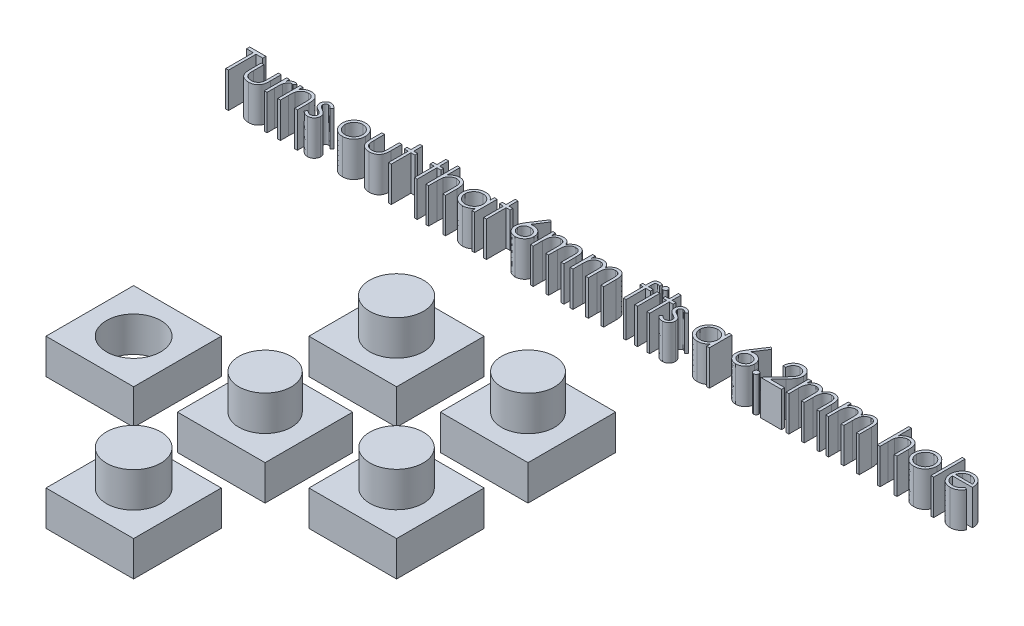
SolidWorks part; units mm, degrees
ref_plane "Front Plane" through (0, 0, 0) normal (0, 0, 1) x (1, 0, 0)
ref_plane "Top Plane" through (0, 0, 0) normal (0, 1, 0) x (1, 0, 0)
ref_plane "Right Plane" through (0, 0, 0) normal (1, 0, 0) x (0, 0, -1)
sketch "Sketch1" plane through (0, 0, 0) normal (0, 1, 0) x (1, 0, 0)
  line L0 (-52.5791, 0) -> (55.194, 0) construction
  line L1 (0, 46.4218) -> (0, -38.957) construction
  line L3 (-5, -5) -> (5, -5)
  line L4 (-5, -5) -> (-5, 5)
  line L5 (-5, 5) -> (5, 5)
  line L6 (5, -5) -> (5, 5)
  line L7 (-5, -5) -> (5, 5) construction
  line L8 (-5, 5) -> (5, -5) construction
  line L9 (-20, -5) -> (-10, -5)
  line L10 (-20, -5) -> (-20, 5)
  line L11 (-20, 5) -> (-10, 5)
  line L12 (-10, -5) -> (-10, 5)
  line L13 (-20, -5) -> (-10, 5) construction
  line L14 (-20, 5) -> (-10, -5) construction
  line L16 (10, -5) -> (20, -5)
  line L17 (10, -5) -> (10, 5)
  line L18 (10, 5) -> (20, 5)
  line L19 (20, -5) -> (20, 5)
  line L20 (10, -5) -> (20, 5) construction
  line L21 (10, 5) -> (20, -5) construction
  line L22 (-5, -20) -> (5, -20)
  line L23 (-5, -20) -> (-5, -10)
  line L24 (-5, -10) -> (5, -10)
  line L25 (5, -20) -> (5, -10)
  line L26 (-5, -20) -> (5, -10) construction
  line L27 (-5, -10) -> (5, -20) construction
  line L28 (-5, 10) -> (5, 10)
  line L29 (-5, 10) -> (-5, 20)
  line L30 (-5, 20) -> (5, 20)
  line L31 (5, 10) -> (5, 20)
  line L32 (-5, 10) -> (5, 20) construction
  line L33 (-5, 20) -> (5, 10) construction
  line L34 (10, 10) -> (20, 10)
  line L35 (10, 10) -> (10, 20)
  line L36 (10, 20) -> (20, 20)
  line L37 (20, 10) -> (20, 20)
  line L38 (10, 10) -> (20, 20) construction
  line L39 (10, 20) -> (20, 10) construction
  circle A0 centre (-15, 0) radius 3.1
  circle A1 centre (0, 0) radius 3
  circle A2 centre (15, 0) radius 3.05
  circle A3 centre (0, -15) radius 3.1
  circle A4 centre (0, 15) radius 3.075
  circle A5 centre (15, 15) radius 3.025
  text T0 "Turns out that 6mm fits a 6.2mm hole"
  point P5 (0, 0)
  point P10 (-15, 0)
  point P20 (-37.0029, 31.7041)
  point P23 (15, 0)
  point P31 (0, -15)
  point P39 (0, 15)
  point P47 (15, 15)
  dimension "D5" = 6.2
  dimension "D7" = 6
  dimension "D10" = 6.1
  dimension "D14" = 6.2
  dimension "D18" = 6.15
  dimension "D22" = 6.05
  dimension "D1" = 10
  dimension "D2" = 10
  dimension "D3" = 10
  dimension "D4" = 10
  dimension "D6" = 5
  dimension "D8" = 10
  dimension "D9" = 10
  dimension "D11" = 5
  dimension "D12" = 10
  dimension "D13" = 10
  dimension "D15" = 5
  dimension "D16" = 10
  dimension "D17" = 10
  dimension "D19" = 5
  dimension "D20" = 10
  dimension "D21" = 10
extrude "Boss-Extrude1" add sketch "Sketch1" along normal blind 4
extrude "Boss-Extrude2" add sketch "Sketch1<3>" along normal blind 8 contours A4 | A5 | A2 | A1 | A3 region at (0, 0, 0) region at (15, 0, 0) region at (0, 0, -15) region at (15, 0, -15)
sketch "Sketch1<3>" plane through (0, 0, 0) normal (0, 1, 0) x (1, 0, 0) same geometry as "Sketch1"
